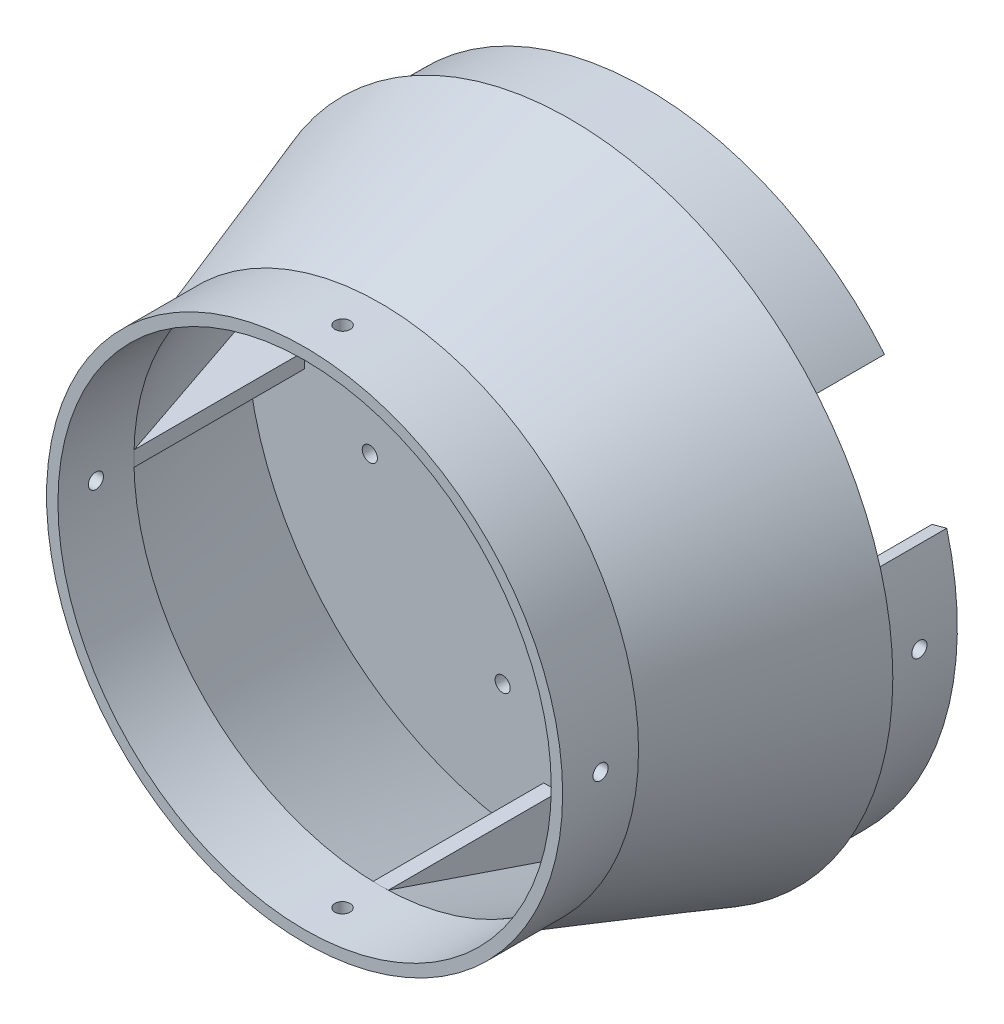
SolidWorks part; units mm, degrees
ref_plane "Front Plane" through (0, 0, 0) normal (0, 0, 1) x (1, 0, 0)
ref_plane "Top Plane" through (0, 0, 0) normal (0, 1, 0) x (1, 0, 0)
ref_plane "Right Plane" through (0, 0, 0) normal (1, 0, 0) x (0, 0, -1)
sketch "Sketch10" plane through (0, 0, 0) normal (0, 1, 0) x (1, 0, 0)
  line L9 (68, 0) -> (85, 50)
  line L10 (65, 0) -> (65, -20)
  line L11 (65, -20) -> (68, -20)
  line L12 (68, -20) -> (68, 0)
  line L13 (85, 50) -> (0, 50)
  line L14 (0, 50) -> (0, 45)
  line L16 (0, 0) -> (0, 90.5218) construction
  line L17 (65, 0) -> (80.3, 45)
  line L18 (0, 45) -> (80.3, 45)
  dimension "D1" = 65
  dimension "D2" = 20
  dimension "D3" = 50
  dimension "D4" = 85
  dimension "D5" = 68
  dimension "D6" = 5
revolve "Revolve2" add sketch "Sketch10" angle 360 about L16
sketch "Sketch12" plane through (0, 0, 0) normal (0, 1, 0) x (1, 0, 0)
  line L4 (-80.3, 45) -> (-65, 0)
  line L5 (-65, 0) -> (-65, 45)
  line L6 (-80.3, 45) -> (80.3, 45) construction
  line L7 (-65, 45) -> (-80.3, 45)
extrude "Boss-Extrude5" add sketch "Sketch12" along normal blind 2 and the other way blind 2
pattern_circular "CirPattern3" count 4 every 90 about axis through (0, 0, -50) along (0, 0, 1) of "Boss-Extrude5"
sketch "Sketch13" plane through (0, 0, -50) normal (0, 0, -1) x (-1, 0, 0)
  arc A0 (70, 42.7083) -> (70, -42.7083) centre (0, 0) ccw
  arc A1 (70, 34.4093) -> (70, -34.4093) centre (0, 0) ccw
  circle A2 centre (0, 0) radius 82 construction
  circle A3 centre (0, 0) radius 78 construction
  circle A4 centre (0, 0) radius 82
  circle A5 centre (0, 0) radius 78
  dimension "D1" = 164
  dimension "D2" = 4
extrude "Boss-Extrude6" add sketch "Sketch13" along normal blind 20 contours A0 A4 A5 A1 region at (-76.7102, 21.5537, -50)
sketch "Sketch14" plane through (0, 0, 0) normal (0, 1, 0) x (1, 0, 0)
  line L0 (-65, -20) -> (65, -20) construction
  circle A0 centre (0, -10) radius 2
  dimension "D1" = 4
  dimension "D2" = 10
extrude "Cut-Extrude1" cut sketch "Sketch14" against normal blind 95
pattern_circular "CirPattern4" count 4 every 90 about axis through (0, 0, 20) along (0, 0, 1) of "Cut-Extrude1"
fillet "Fillet1" radius 5 1 edges at (-78, 0, -50)
sketch "Sketch16" plane through (0, 0, 0) normal (0, 1, 0) x (1, 0, 0)
  line L0 (85, 50) -> (-85, 50) construction
  circle A0 centre (0, 60) radius 2
  dimension "D1" = 4
  dimension "D2" = 10
extrude "Cut-Extrude2" cut sketch "Sketch16" against normal blind 94
pattern_circular "CirPattern5" count 2 every 90 about axis through (0, 0, -70) along (0, 0, -1) of "Cut-Extrude2" other way count 2
sketch "Sketch17" plane through (0, 0, -50) normal (0, 0, -1) x (-1, 0, 0)
  line L0 (0, 0) -> (-47.8133, 12.8115) construction
  line L1 (0, 0) -> (-12.8115, 47.8133) construction
  circle A0 centre (-47.8133, 12.8115) radius 2
  circle A4 centre (-12.8115, 47.8133) radius 2
  circle A5 centre (12.8115, -47.8133) radius 2
  circle A6 centre (47.8133, -12.8115) radius 2
  point P12 (0, 0)
  point P16 (0, 0)
  dimension "D1" = 4
  dimension "D2" = 49.5
  dimension "D4" = 60
  dimension "D3" = 2
  dimension "D5" = 2
extrude "Cut-Extrude4" cut sketch "Sketch17" against normal blind 900
sketch "Sketch19" plane through (0, 0, -70) normal (0, 0, -1) x (-1, 0, 0)
  line L0 (0, 0) -> (0, 85) construction
  line L1 (0, 0) -> (-79.2059, 21.2232)
  line L6 (0, 0) -> (-62.8156, 52.7086)
  circle A0 centre (0, 0) radius 85 construction
  arc A2 (-62.8156, 52.7086) -> (-79.2059, 21.2232) centre (0, 0) ccw
  dimension "D1" = 75
  dimension "D2" = 50
extrude "Cut-Extrude7" cut sketch "Sketch19" against normal blind 20
mirror "Mirror1" about plane through (0, 0, 0) normal (1, 0, 0) of "Cut-Extrude7"
